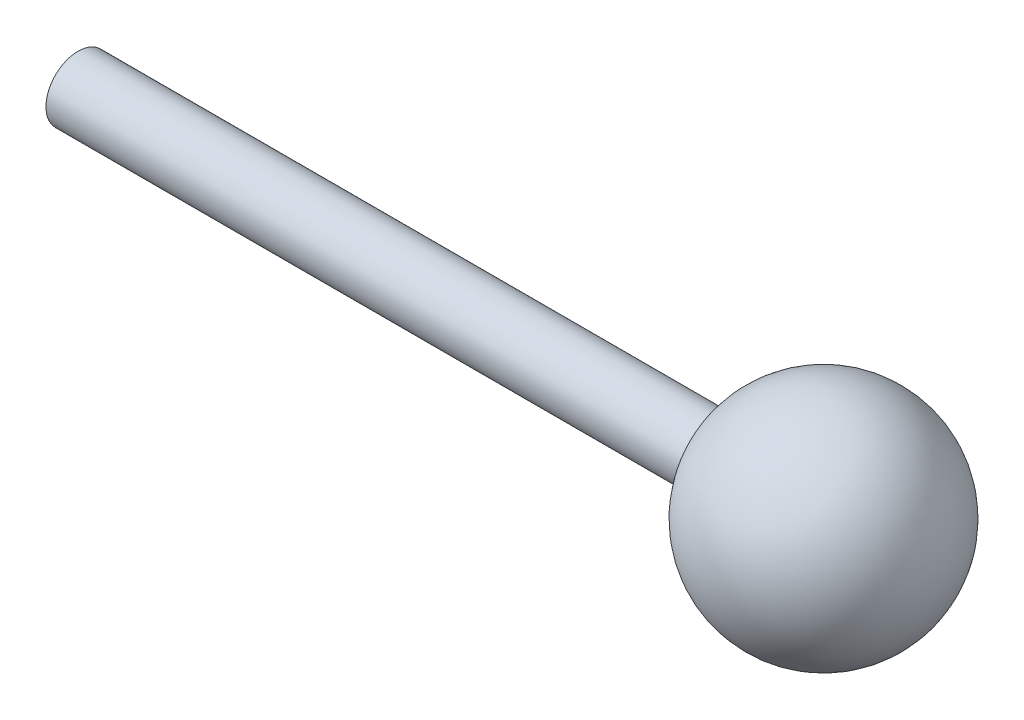
SolidWorks part; units mm, degrees
ref_plane "Front Plane" through (0, 0, 0) normal (0, 0, 1) x (1, 0, 0)
ref_plane "Top Plane" through (0, 0, 0) normal (0, 1, 0) x (1, 0, 0)
ref_plane "Right Plane" through (0, 0, 0) normal (1, 0, 0) x (0, 0, -1)
sketch "Sketch1" plane through (0, 0, 0) normal (1, 0, 0) x (0, 0, -1)
  circle A0 centre (-31.7842, 14.9727) radius 0.75
extrude "Boss-Extrude1" add sketch "Sketch1" along normal blind 15
dome "Dome1" faces to dome 1 distance 5 reverse direction no elliptical dome no face at (15, 14.9727, 31.0342) parameters "D1"=5
